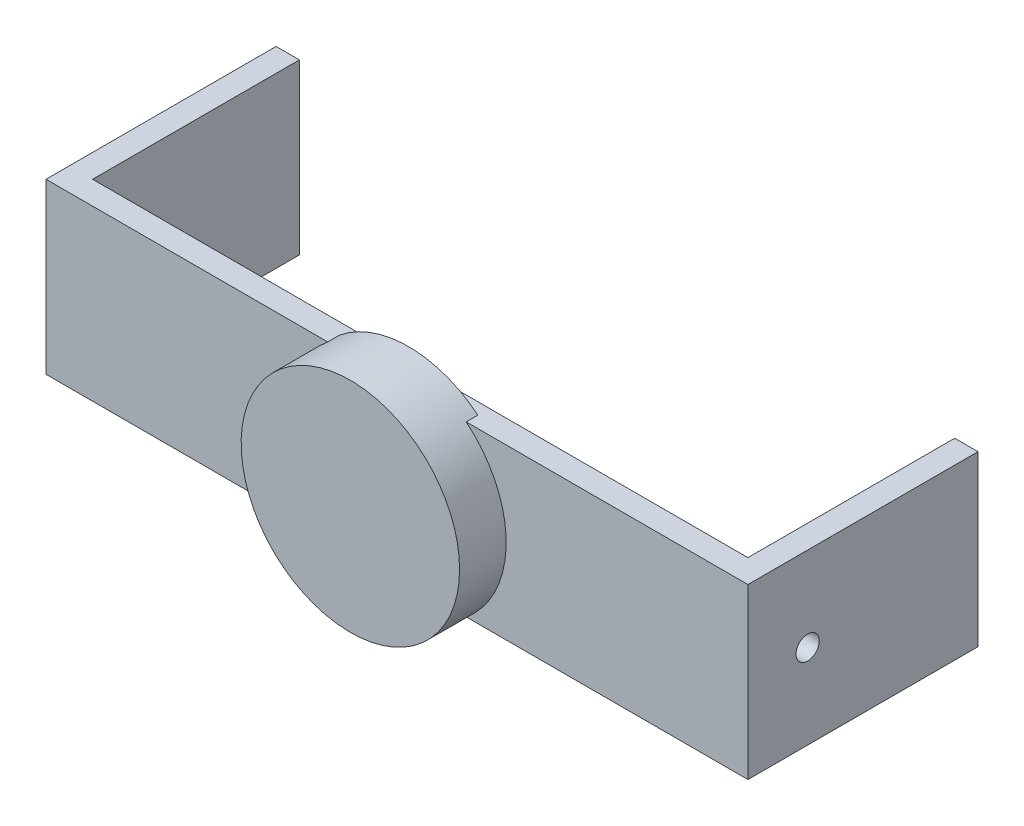
SolidWorks part; units mm, degrees
ref_plane "Front Plane" through (0, 0, 0) normal (0, 0, 1) x (1, 0, 0)
ref_plane "Top Plane" through (0, 0, 0) normal (0, 1, 0) x (1, 0, 0)
ref_plane "Right Plane" through (0, 0, 0) normal (1, 0, 0) x (0, 0, -1)
ref_plane "Plane1" through (0, 0, 190) normal (0, 0, 1) x (1, 0, 0)
sketch "Sketch1" plane through (0, 0, 190) normal (0, 0, 1) x (1, 0, 0)
  circle A0 centre (300, 300) radius 75
extrude "Boss-Extrude1" add sketch "Sketch1" along normal blind 40
ref_plane "Plane2" through (0, 0, 182) normal (0, 0, 1) x (1, 0, 0)
sketch "Sketch2" plane through (0, 0, 182) normal (0, 0, 1) x (1, 0, 0)
  line L1 (59, 242) -> (541, 242)
  line L2 (59, 242) -> (59, 358)
  line L3 (59, 358) -> (541, 358)
  line L4 (541, 242) -> (541, 358)
extrude "Boss-Extrude2" add sketch "Sketch2" along normal blind 16
ref_plane "Plane3" through (525, 0, 0) normal (1, 0, 0) x (0, 0, -1)
sketch "Sketch3" plane through (525, 0, 0) normal (1, 0, 0) x (0, 0, -1)
  line L0 (-198, 358) -> (-182, 358) construction
  line L1 (-40, 242) -> (-187, 242)
  line L2 (-40, 242) -> (-40, 358)
  line L3 (-40, 358) -> (-187, 358)
  line L4 (-187, 242) -> (-187, 358)
extrude "Boss-Extrude3" add sketch "Sketch3" along normal blind 16
ref_plane "Plane4" through (59, 0, 0) normal (1, 0, 0) x (0, 0, -1)
sketch "Sketch4" plane through (59, 0, 0) normal (1, 0, 0) x (0, 0, -1)
  line L0 (-198, 358) -> (-40, 358) construction
  line L1 (-40, 242) -> (-187, 242)
  line L2 (-40, 242) -> (-40, 358)
  line L3 (-40, 358) -> (-187, 358)
  line L4 (-187, 242) -> (-187, 358)
extrude "Boss-Extrude4" add sketch "Sketch4" along normal blind 16
sketch "Sketch5" plane through (541, 0, 0) normal (1, 0, 0) x (0, 0, -1)
  circle A0 centre (-157, 300) radius 8
extrude "Cut-Extrude1" cut sketch "Sketch5" against normal blind 502
